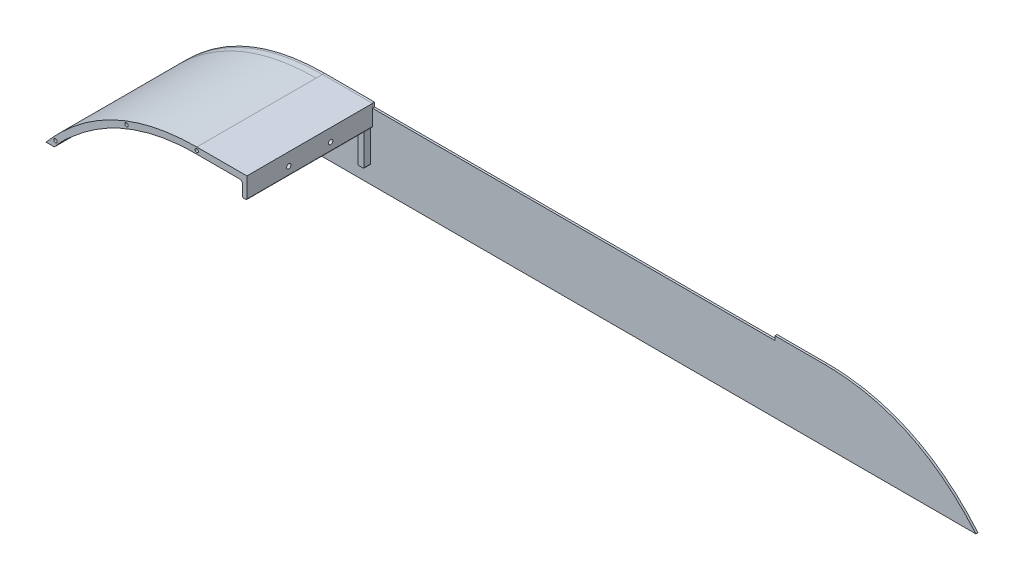
SolidWorks part; units mm, degrees
ref_plane "Front Plane" through (0, 0, 0) normal (0, 0, 1) x (1, 0, 0)
ref_plane "Top Plane" through (0, 0, 0) normal (0, 1, 0) x (1, 0, 0)
ref_plane "Right Plane" through (0, 0, 0) normal (1, 0, 0) x (0, 0, -1)
sketch "Sketch1" plane through (0, 0, 0) normal (0, 0, 1) x (1, 0, 0)
  line L0 (0, 0) -> (-304.8, 0)
  line L1 (0, 0) -> (609.6, 0)
  line L2 (0, 0) -> (0, 107.95) construction
  line L3 (0, 107.95) -> (609.6, 107.95)
  line L4 (609.6, 0) -> (609.6, 107.95) construction
  line L5 (609.6, 0) -> (914.4, 0)
  line L6 (304.8, -1000) -> (304.8, 49000) construction
  line L7 (0, 107.95) -> (-76.2, 107.95)
  line L8 (609.6, 107.95) -> (685.8, 107.95)
  spline S0 degree 2 poles (-304.8, 0) (-213.404, 107.36) (-76.2, 107.95) knots 0 0 0 1 1 1
  spline S1 degree 2 poles (914.4, 0) (823.004, 107.36) (685.8, 107.95) knots 0 0 0 1 1 1
  point P11 (304.8, 0)
  dimension "D1" = 609.6
  dimension "D2" = 107.95
  dimension "D3" = 304.8
  dimension "D4" = 76.2
extrude "Boss-Extrude1" add sketch "Sketch1" along normal blind 3.175
sketch "Sketch2" plane through (0, 0, 3.175) normal (0, 0, 1) x (1, 0, 0)
  line L8 (685.8, 107.95) -> (-76.2, 107.95) construction
  line L11 (0, 107.95) -> (609.6, 107.95)
  line L12 (0, 107.95) -> (0, 101.6) construction
  line L13 (0, 101.6) -> (609.6, 101.6)
  line L14 (609.6, 107.95) -> (609.6, 101.6) construction
  line L15 (-0.254, 107.95) -> (-0.254, 101.6)
  line L16 (609.854, 107.95) -> (609.854, 101.6)
  line L19 (609.6, 107.95) -> (609.854, 107.95)
  line L20 (609.6, 101.6) -> (609.854, 101.6)
  line L21 (-0.254, 107.95) -> (0, 107.95)
  line L22 (-0.254, 101.6) -> (0, 101.6)
  dimension "D1" = 609.6
  dimension "D2" = 6.35
  dimension "D3" = 0.254
  dimension "D4" = 0.254
extrude "Cut-Extrude1" cut sketch "Sketch2" against normal through all
sketch "Sketch3" plane through (0, 0, 3.175) normal (0, 0, 1) x (1, 0, 0)
  line L5 (-76.0908, 82.5502) -> (-76.2, 107.95) construction
  line L6 (685.8, 107.95) -> (609.854, 107.95)
  line L7 (609.854, 107.95) -> (609.854, 101.6)
  line L8 (609.854, 101.6) -> (-0.254, 101.6)
  line L9 (-0.254, 101.6) -> (-0.254, 107.95)
  line L10 (-0.254, 107.95) -> (-76.2, 107.95)
  line L11 (-304.8, 0) -> (914.4, 0)
  line L19 (-304.8, 0) -> (-254.508, 0)
  line L20 (-304.8, 0) -> (914.4, 0) construction
  line L21 (-254.508, 0) -> (-254.508, 15.3448)
  line L22 (-76.2, 107.95) -> (-0.254, 107.95)
  line L23 (-0.254, 107.95) -> (-0.254, 76.2)
  line L24 (-0.254, 76.2) -> (-6.604, 76.2)
  line L25 (-6.604, 76.2) -> (-6.604, 82.5502)
  line L26 (-6.604, 82.5502) -> (-76.0908, 82.5502)
  parabola Q2 (-76.2, 107.95) -> (-304.8, 0) focus (-138.8032, -41.5009) apex (-192.9562, 84.7198)
  parabola Q3 (914.4, 0) -> (685.8, 107.95) focus (748.4032, -41.5009) apex (802.5562, 84.7198)
  parabola Q4 (-76.2, 107.95) -> (-304.8, 0) focus (-138.8032, -41.5009) apex (-192.9562, 84.7198)
  spline S0 degree 1 poles (-76.0908, 82.5502) (-285.4592, -16.4649) knots 0 0 1 1 construction
  spline S1 degree 3 poles (-76.0908, 82.5502) (-78.7263, 82.5389) (-84.0207, 82.4515) (-94.414, 82.0204) (-107.175, 81.0024) (-122.0857, 79.0209) (-140.2937, 75.5918) (-157.8592, 70.8643) (-175.9104, 64.4537) (-194.5198, 56.4637) (-212.4049, 46.7322) (-228.6865, 35.996) (-240.414, 27.3) (-249.9299, 19.4397) (-257.5609, 12.6326) (-263.3873, 7.1473) (-268.2089, 2.3627) (-271.8925, -1.4301) (-275.5622, -5.3024) (-280.0978, -10.2646) (-283.6939, -14.3913) (-285.4592, -16.4649) knots 0.497516 0.497516 0.497516 0.497516 0.497684 0.497853 0.498189 0.498526 0.498863 0.499456 0.499793 0.50021 0.500884 0.501221 0.501558 0.501878 0.502046 0.502231 0.502399 0.502483 0.502568 0.502737 0.502905 0.502905 0.502905 0.502905 only from (-76.0908, 82.5502) to (-270.5007, 0) construction
  spline S2 degree 2 poles (-254.508, 15.3448) (-177.7983, 82.8932) (-76.0908, 82.5502) knots 0 0 0 1 1 1
  dimension "D2" = 31.75
  dimension "D3" = 6.35
  dimension "D5" = 50.292
  dimension "D1" = 0
  dimension "D4" = 25.4
extrude "Boss-Extrude2" add sketch "Sketch3" along normal blind 9.525
sketch "Sketch5" plane through (0, 0, 12.7) normal (0, 0, 1) x (1, 0, 0)
  line L7 (-304.8, 0) -> (-292.1, 0)
  line L8 (-76.0372, 98.4251) -> (-6.604, 98.4251)
  line L9 (-6.604, 98.4251) -> (-6.604, 82.5502)
  line L14 (-304.8, 0) -> (-254.508, 0)
  line L15 (-254.508, 0) -> (-254.508, 15.3448)
  line L16 (-76.0908, 82.5502) -> (-6.604, 82.5502)
  line L17 (-6.604, 82.5502) -> (-6.604, 76.2)
  line L18 (-6.604, 76.2) -> (-0.254, 76.2)
  line L19 (-0.254, 76.2) -> (-0.254, 107.95)
  line L20 (-0.254, 107.95) -> (-76.2, 107.95)
  line L24 (-6.604, 82.5502) -> (-6.604, 76.2)
  line L25 (-6.604, 76.2) -> (-0.254, 76.2)
  line L26 (-0.254, 76.2) -> (-0.254, 107.95)
  line L27 (-0.254, 107.95) -> (-76.2, 107.95)
  parabola Q4 (-76.2, 107.95) -> (-304.8, 0) focus (-138.8032, -41.5009) apex (-192.9562, 84.7198)
  parabola Q5 (-254.508, 15.3448) -> (-76.0908, 82.5502) focus (-126.3995, -51.2914) apex (-169.7975, 66.5726)
  parabola Q6 (-76.2, 107.95) -> (-304.8, 0) focus (-138.8032, -41.5009) apex (-192.9562, 84.7198)
  parabola Q7 (-254.508, 15.3448) -> (-76.0908, 82.5502) focus (-126.3995, -51.2914) apex (-169.7975, 66.5726) construction
  spline S0 degree 1 poles (-264.9993, 27.259) (-76.0372, 98.4251) knots 0 0 1 1 construction
  spline S1 degree 3 poles (-264.9993, 27.259) (-263.3249, 28.7335) (-259.9376, 31.6547) (-253.107, 37.2998) (-244.419, 44.0244) (-233.7687, 51.5472) (-219.2659, 60.8476) (-200.5783, 71.0931) (-177.2837, 81.1523) (-153.1553, 88.9561) (-132.3866, 93.5719) (-115.3933, 96.1333) (-102.4647, 97.4901) (-91.5371, 98.1519) (-82.7134, 98.4012) (-78.2591, 98.4326) (-76.0372, 98.4251) knots 0.497832 0.497832 0.497832 0.497832 0.497965 0.498098 0.498363 0.498629 0.498895 0.499427 0.499958 0.50049 0.501022 0.501287 0.501553 0.501819 0.501952 0.502085 0.502085 0.502085 0.502085
  spline S2 degree 2 poles (-264.9993, 27.259) (-280.0432, 15.0907) (-292.1, 0) knots 0 0 0 1 1 1
  dimension "D3" = 12.7
  dimension "D1" = 0
  dimension "D2" = 15.875
extrude "Boss-Extrude3" add sketch "Sketch5" along normal blind 180.975
sketch "Sketch6" plane through (0, 0, 12.7) normal (0, 0, 1) x (1, 0, 0)
  line L1 (-254.508, 0) -> (-226.4253, 0)
  line L2 (-254.508, 0) -> (-254.508, 28.575)
  line L3 (-254.508, 28.575) -> (-226.4253, 28.575)
  line L4 (-226.4253, 0) -> (-226.4253, 28.575)
  dimension "D1" = 28.575
extrude "Cut-Extrude2" cut sketch "Sketch6" against normal up to surface (9.525 mm away) up to face at (204.1979, 60.3971, 3.175)
sketch "Sketch7" plane through (0, 0, 12.7) normal (0, 0, 1) x (1, 0, 0)
  line L0 (-292.1, 0) -> (-254.508, 0) construction
  line L1 (-254.508, 0) -> (-254.508, 28.575) construction
  line L2 (-76.0651, 90.1702) -> (-9.6958, 90.1702) construction
  line L3 (-6.604, 98.4251) -> (-6.604, 76.2) construction
  circle A0 centre (-267.208, 10.16) radius 3.275
  circle A1 centre (-175.3658, 72.6223) radius 3.275
  circle A3 centre (-57.404, 90.1702) radius 3.275
  parabola Q0 (-238.3942, 28.575) -> (-76.0908, 82.5502) focus (-126.3995, -51.2914) apex (-169.7975, 66.5726) construction
  parabola Q1 (-238.3942, 28.575) -> (-76.0908, 82.5502) focus (-126.3995, -51.2914) apex (-169.7975, 66.5726) construction
  spline S0 degree 1 poles (-243.0182, 34.6317) (-76.0651, 90.1702) knots 0 0 1 1 construction
  spline S1 degree 3 poles (-243.0182, 34.6317) (-239.9935, 36.9409) (-233.8311, 41.4586) (-224.4638, 47.7679) (-214.9157, 53.6525) (-202.0674, 60.8581) (-190.551, 66.4075) (-178.8009, 71.3309) (-171.8366, 73.9914) (-159.5844, 78.2202) (-143.5556, 82.8056) (-125.3458, 86.3973) (-110.4698, 88.391) (-99.1613, 89.4468) (-89.6088, 89.961) (-81.8979, 90.1535) (-78.0064, 90.1767) (-76.0651, 90.1702) knots 0.498271 0.498271 0.498271 0.498271 0.49851 0.498748 0.498986 0.499225 0.499694 0.499813 0.500051 0.500178 0.500655 0.501131 0.50137 0.501608 0.501846 0.501966 0.502085 0.502085 0.502085 0.502085 construction
  dimension "D1" = 6.55
  dimension "D5" = 6.55
  dimension "D6" = 6.55
  dimension "D2" = 10.16
  dimension "D4" = 12.7
  dimension "D7" = 50.8
  dimension "D3" = 7.62
extrude "Cut-Extrude3" cut sketch "Sketch7" against normal through all
sketch "Sketch8" plane through (-0.254, 0, 0) normal (1, 0, 0) x (0, 0, -1)
  line L0 (-1151.3542, 88.9) -> (48848.6458, 88.9) construction
  line L1 (-193.675, 76.2) -> (-3.175, 76.2) construction
  line L2 (-3.175, 76.2) -> (-3.175, 101.6) construction
  circle A2 centre (-66.675, 88.9) radius 3.325
  circle A5 centre (-130.175, 88.9) radius 3.325
  dimension "D2" = 6.65
  dimension "D4" = 63.5
  dimension "D1" = 12.7
  dimension "D3" = 2
extrude "Cut-Extrude5" cut sketch "Sketch8" against normal up to surface (6.35 mm away) up to face at (-6.604, 85.7251, 69.85)
sketch "Sketch9" plane through (0, 0, 193.675) normal (0, 0, 1) x (1, 0, 0)
  circle A0 centre (-290.3708, 9.1426) radius 2.6
  circle A1 centre (-182.7594, 83.8165) radius 2.6
  circle A2 centre (-76.1798, 103.25) radius 2.6
  parabola Q0 (-76.2, 107.95) -> (-304.8, 0) focus (-138.8032, -41.5009) apex (-192.9562, 84.7198) construction
  parabola Q1 (-76.2, 107.95) -> (-304.8, 0) focus (-138.8032, -41.5009) apex (-192.9562, 84.7198) construction
  spline S0 degree 1 poles (-76.1798, 103.25) (-301.2212, -3.0467) knots 0 0 1 1 construction
  spline S1 degree 3 poles (-76.1798, 103.25) (-78.9851, 103.238) (-84.6167, 103.1451) (-95.7036, 102.6853) (-109.3519, 101.5971) (-125.3575, 99.4709) (-145.1456, 95.7451) (-161.7727, 91.2541) (-177.9517, 85.7316) (-188.5878, 81.5829) (-206.0869, 73.7491) (-227.5653, 62.0602) (-249.2337, 46.8941) (-265.8815, 33.1047) (-277.7275, 22.2059) (-286.3, 13.5161) (-292.1052, 7.2837) (-296.2196, 2.7435) (-299.3516, -0.8505) (-301.2212, -3.0467) knots 0.497516 0.497516 0.497516 0.497516 0.497684 0.497853 0.498189 0.498526 0.498863 0.499468 0.499636 0.499973 0.50021 0.500884 0.501558 0.501895 0.502231 0.502544 0.502628 0.502737 0.502905 0.502905 0.502905 0.502905 construction
  dimension "D2" = 5.2
  dimension "D3" = 5.2
  dimension "D4" = 5.2
  dimension "D1" = 4.7
extrude "Cut-Extrude6" cut sketch "Sketch9" against normal blind 12.7
sketch "Sketch11" plane through (-254.508, 0, 0) normal (1, 0, 0) x (0, 0, -1)
  line L0 (-3.175, 0) -> (-3.175, 28.575) construction
  line L1 (-12.7, 0) -> (-3.175, 0) construction
  circle A0 centre (-7.1374, 3.9751) radius 1.9
  circle A3 centre (-7.1374, 21.4251) radius 1.9
  dimension "D3" = 3.8
  dimension "D1" = 3.9624
  dimension "D2" = 3.9751
  dimension "D4" = 2
extrude "Boss-Extrude5" add sketch "Sketch11" along normal blind 10.16
sketch "Sketch14" plane through (0, 82.5502, 0) normal (0, -1, 0) x (1, 0, 0)
  line L5 (-76.0372, 12.7) -> (-6.604, 12.7) construction
  line L6 (-0.254, 3.175) -> (-12.954, 3.175)
  line L7 (-0.254, 3.175) -> (-0.254, 12.7)
  line L8 (-0.254, 12.7) -> (-12.954, 12.7)
  line L9 (-12.954, 3.175) -> (-12.954, 12.7)
  dimension "D1" = 12.7
extrude "Boss-Extrude8" add sketch "Sketch14" along normal offset from surface (57.1502 mm away) 25.4 up to face at (-48.3616, 0, 43.4975)
sketch "Sketch17" plane through (-0.254, 0, 0) normal (1, 0, 0) x (0, 0, -1)
  line L1 (-12.7, 76.2) -> (-3.175, 76.2)
  line L2 (-12.7, 76.2) -> (-12.7, 25.4)
  line L3 (-12.7, 25.4) -> (-3.175, 25.4)
  line L4 (-3.175, 76.2) -> (-3.175, 25.4)
  point P6 (-12.7, 75.8973)
  point P7 (-12.7, 76.2)
extrude "Cut-Extrude9" cut sketch "Sketch17" against normal blind 3.175
fillet "Fillet1" radius 5 1 edges at (-6.604, 98.4251, 103.1875)
fillet "Fillet2" radius 2 2 edges at (-238.3942, 28.575, 7.9375) (-254.508, 28.575, 7.9375)
fillet "Fillet3" radius 1 1 edges at (-292.1, 0, 103.1875)
fillet "Fillet8" radius 5 1 edges at (-12.954, 82.5502, 7.9375)
fillet "Fillet9" radius 1.5 4 edges at (-0.254, 76.2, 98.425) (-6.604, 76.2, 103.1875) (-12.954, 25.4, 7.9375) (-3.429, 25.4, 7.9375)
fillet "Fillet10" radius 1.5 1 edges at (-3.429, 76.2, 7.9375)
split "Split2" bodies to split 122 resulting bodies 123 124 split by face at (69.9115, 52.5633, 3.175)
